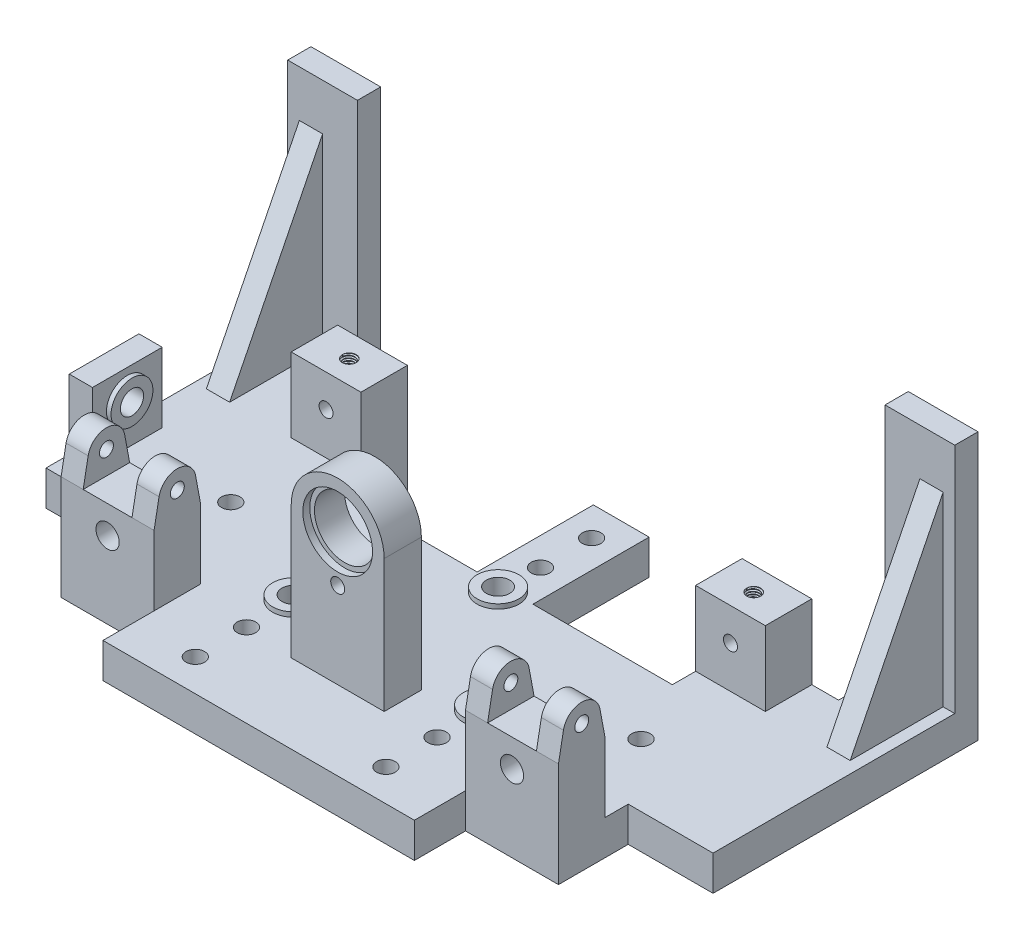
SolidWorks part; units mm, degrees
material "铸造碳钢"
ref_plane "前视基准面" through (0, 0, 0) normal (0, 0, 1) x (1, 0, 0)
ref_plane "上视基准面" through (0, 0, 0) normal (0, 1, 0) x (1, 0, 0)
ref_plane "右视基准面" through (0, 0, 0) normal (1, 0, 0) x (0, 0, -1)
sketch "草图1" plane through (0, 0, 0) normal (0, 1, 0) x (1, 0, 0)
  line L1 (-67, 0) -> (67, 0)
  line L9 (-143.5, 52) -> (-107, 52)
  line L10 (-107, 52) -> (-107, 22)
  line L11 (143.5, 52) -> (107, 52)
  line L12 (107, 52) -> (107, 22)
  line L13 (-107, 22) -> (-67, 22)
  line L14 (-67, 22) -> (-67, 0)
  line L15 (107, 22) -> (67, 22)
  line L16 (67, 22) -> (67, 0)
  line L21 (-72, 136) -> (-72, 106)
  line L22 (-72, 106) -> (-12, 106)
  line L25 (12, 106) -> (72, 106)
  line L26 (72, 106) -> (72, 136)
  line L27 (-12, 156) -> (-12, 106)
  line L28 (-12, 156) -> (12, 156)
  line L29 (12, 156) -> (12, 106)
  line L30 (-72, 136) -> (-143.5, 136)
  line L31 (-143.5, 136) -> (-143.5, 52)
  line L32 (72, 136) -> (143.5, 136)
  line L33 (143.5, 136) -> (143.5, 52)
  point P18 (0, 0)
  dimension "D2" = 60
  dimension "D3" = 71.5
  dimension "D4" = 84
  dimension "D5" = 60
  dimension "D6" = 50
  dimension "D7" = 287
  dimension "D8" = 71.5
  dimension "D9" = 36.5
  dimension "D10" = 76.5
  dimension "D11" = 36.5
  dimension "D12" = 76.5
  dimension "D13" = 22
  dimension "D14" = 52
  dimension "D18" = 30
extrude "凸台-拉伸1" add sketch "草图1" along normal blind 15
sketch "草图3" plane through (0, 15, 0) normal (0, 1, 0) x (1, 0, 0)
  line L0 (-133.5, 92) -> (-133.5, 62)
  line L1 (-133.5, 62) -> (-143.5, 62)
  line L2 (-143.5, 62) -> (-143.5, 92)
  line L3 (-143.5, 92) -> (-133.5, 92)
  line L4 (-67, 0) -> (67, 0) construction
  line L7 (-143.5, 136) -> (-143.5, 52) construction
  dimension "D1" = 30
  dimension "D2" = 10
  dimension "D3" = 62
extrude "凸台-拉伸2" add sketch "草图3" along normal blind 30
sketch "草图5" plane through (0, 15, 0) normal (0, 1, 0) x (1, 0, 0)
  line L0 (-107, 42) -> (-107, 22)
  line L1 (-107, 22) -> (-67, 22)
  line L2 (-67, 22) -> (-67, 42)
  line L3 (-67, 42) -> (-107, 42)
  line L4 (67, 42) -> (67, 22)
  line L5 (67, 22) -> (107, 22)
  line L6 (107, 22) -> (107, 42)
  line L7 (107, 42) -> (67, 42)
  line L8 (-67, 0) -> (67, 0) construction
  line L9 (-133.5, 62) -> (-133.5, 92) construction
  dimension "D1" = 20
  dimension "D2" = 40
  dimension "D3" = 20
  dimension "D4" = 40
  dimension "D5" = 42
  dimension "D6" = 42
  dimension "D7" = 26.5
  dimension "D8" = 134
extrude "凸台-拉伸3" add sketch "草图5" along normal blind 30
sketch "草图2" plane through (0, 15, 0) normal (0, 1, 0) x (1, 0, 0)
  line L0 (132.9483, 103) -> (219.6658, 103) construction
  line L1 (123.0215, 56) -> (237.8074, 56) construction
  line L2 (-41, 68.6858) -> (-41, 50.7818) construction
  line L3 (41, 68.6858) -> (41, 53.2784) construction
  line L4 (0, 122.8842) -> (0, 97.7435) construction
  line L6 (-133.5, 62) -> (-133.5, 92) construction
  line L7 (-67, 42) -> (-107, 42) construction
  circle A1 centre (0, 103) radius 5
  circle A2 centre (-41, 56) radius 5
  circle A3 centre (41, 56) radius 5
  dimension "D1" = 10
  dimension "D2" = 10
  dimension "D3" = 10
  dimension "D4" = 14
  dimension "D5" = 47
  dimension "D6" = 92.5
  dimension "D7" = 82
  dimension "D8" = 133.5
extrude "切除-拉伸1" cut sketch "草图2" against normal blind 13
sketch "草图4" plane through (-133.5, 0, 0) normal (1, 0, 0) x (0, 0, -1)
  line L0 (92, 45) -> (92, 15) construction
  line L1 (62, 15) -> (92, 15) construction
  circle A0 centre (77, 33) radius 5
  dimension "D1" = 10
  dimension "D2" = 15
  dimension "D3" = 18
extrude "切除-拉伸2" cut sketch "草图4" against normal up to next
sketch "草图6" plane through (0, 0, -42) normal (0, 0, -1) x (-1, 0, 0)
  line L0 (67, 15) -> (107, 15) construction
  line L1 (-107, 15) -> (-67, 15) construction
  line L2 (67, 45) -> (67, 15) construction
  line L3 (-67, 45) -> (-67, 15) construction
  circle A0 centre (87, 33) radius 5
  circle A1 centre (-87, 33) radius 5
  dimension "D1" = 10
  dimension "D2" = 10
  dimension "D3" = 18
  dimension "D4" = 18
  dimension "D5" = 20
  dimension "D6" = 20
extrude "切除-拉伸3" cut sketch "草图6" against normal up to next
sketch "草图7" plane through (-133.5, 0, 0) normal (1, 0, 0) x (0, 0, -1)
  circle A0 centre (77, 33) radius 9
  circle A1 centre (77, 33) radius 5 construction
  circle A2 centre (77, 33) radius 5
  dimension "D1" = 18
extrude "凸台-拉伸4" add sketch "草图7" along normal blind 2
sketch "草图8" plane through (0, 0, -42) normal (0, 0, -1) x (-1, 0, 0)
  circle A0 centre (87, 33) radius 5 construction
  circle A1 centre (-87, 33) radius 5 construction
  circle A2 centre (87, 33) radius 5
  circle A3 centre (-87, 33) radius 5
  circle A4 centre (-87, 33) radius 9
  circle A5 centre (87, 33) radius 9
  dimension "D1" = 18
  dimension "D2" = 18
extrude "凸台-拉伸5" add sketch "草图8" along normal blind 2
sketch "草图9" plane through (0, 15, 0) normal (0, 1, 0) x (1, 0, 0)
  circle A0 centre (-41, 56) radius 9
  circle A1 centre (0, 103) radius 9
  circle A2 centre (41, 56) radius 9
  circle A3 centre (-41, 56) radius 5 construction
  circle A4 centre (0, 103) radius 5 construction
  circle A5 centre (41, 56) radius 5 construction
  circle A6 centre (-41, 56) radius 5
  circle A7 centre (0, 103) radius 5
  circle A8 centre (41, 56) radius 5
  dimension "D1" = 18
  dimension "D2" = 18
  dimension "D3" = 18
extrude "凸台-拉伸6" add sketch "草图9" along normal blind 2
sketch "草图11" plane through (0, 15, 0) normal (0, 1, 0) x (1, 0, 0)
  line L0 (-133.5, 62) -> (-133.5, 92) construction
  line L1 (-20, 50) -> (20, 50)
  line L2 (-20, 50) -> (-20, 34)
  line L3 (-20, 34) -> (20, 34)
  line L4 (20, 50) -> (20, 34)
  line L7 (-67, 0) -> (67, 0) construction
  dimension "D1" = 40
  dimension "D2" = 16
  dimension "D3" = 113.5
  dimension "D4" = 34
extrude "凸台-拉伸7" add sketch "草图11" along normal blind 57
sketch "草图12" plane through (0, 72, 0) normal (0, 1, 0) x (1, 0, 0)
  line L5 (0, 34) -> (-20, 34)
  line L6 (-20, 34) -> (20, 34) construction
  line L7 (-20, 34) -> (-20, 50)
  line L8 (-20, 50) -> (0, 50)
  line L9 (20, 50) -> (-20, 50) construction
  line L10 (0, 50) -> (0, 34)
revolve "旋转1" add sketch "草图12" angle 180 about L10 reverse direction yes
sketch "草图13" plane through (0, 0, -34) normal (0, 0, 1) x (1, 0, 0)
  circle A0 centre (0, 72) radius 15
  arc A1 (20, 72) -> (-20, 72) centre (0, 72) ccw construction
  dimension "D1" = 30
extrude "切除-拉伸5" cut sketch "草图13" against normal blind 3 and the other way through all
sketch "草图14" plane through (0, 0, -37) normal (0, 0, 1) x (1, 0, 0)
  circle A0 centre (0, 72) radius 13
  dimension "D1" = 26
extrude "切除-拉伸6" cut sketch "草图14" against normal up to next
sketch "草图15" plane through (0, 0, -34) normal (0, 0, 1) x (1, 0, 0)
  circle A0 centre (0, 72) radius 20 construction
  circle A1 centre (0, 52) radius 3
  dimension "D1" = 40
  dimension "D2" = 6
extrude "切除-拉伸7" cut sketch "草图15" against normal blind 12
sketch "草图10" plane through (0, 15, 0) normal (0, 1, 0) x (1, 0, 0)
  line L0 (-67, 42) -> (-107, 42) construction
  line L1 (67, 42) -> (67, 22) construction
  line L2 (107, 42) -> (67, 42) construction
  line L3 (-67, 22) -> (-67, 42) construction
  line L4 (0, 103) -> (0, 157.8551) construction
  line L5 (-133.5, 62) -> (-133.5, 92) construction
  line L6 (-67, 42) -> (-107, 42) construction
  line L7 (107, 42) -> (67, 42) construction
  circle A0 centre (-41, 35.75) radius 4
  circle A1 centre (41, 35.75) radius 4
  circle A2 centre (-41, 13.75) radius 4
  circle A3 centre (41, 13.75) radius 4
  circle A6 centre (-91, 79) radius 4
  circle A7 centre (0, 121.25) radius 4
  circle A8 centre (0, 143.25) radius 4
  circle A9 centre (85.5, 79) radius 4
  circle A10 centre (0, 103) radius 5 construction
  dimension "D2" = 8
  dimension "D3" = 8
  dimension "D7" = 8
  dimension "D8" = 8
  dimension "D10" = 22
  dimension "D11" = 18.25
  dimension "D12" = 42.5
  dimension "D13" = 37
  dimension "D14" = 8
  dimension "D15" = 8
  dimension "D18" = 8
  dimension "D19" = 8
  dimension "D1" = 6.25
  dimension "D4" = 6.25
  dimension "D5" = 26
  dimension "D6" = 26
  dimension "D9" = 22
  dimension "D16" = 37
  dimension "D17" = 176.5
extrude "切除-拉伸4" cut sketch "草图10" against normal through all
ref_plane "基准面1" through (0, 45, 0) normal (0, 1, 0) x (1, 0, 0)
sketch "草图16" plane through (107, 0, 0) normal (1, 0, 0) x (0, 0, -1)
  line L0 (22, 45) -> (24.1352, 56.4648)
  line L1 (42, 45) -> (39.8648, 56.4648)
  line L2 (22, 45) -> (42, 45) construction
  line L3 (22, 45) -> (42, 45)
  arc A2 (39.8648, 56.4648) -> (24.1352, 56.4648) centre (32, 55) ccw
  dimension "D1" = 10
  dimension "D2" = 16
  dimension "D3" = 10
extrude "凸台-拉伸8" add sketch "草图16" against normal blind 40
sketch "草图17" plane through (45, 45, 0) normal (0, -1, 0) x (0, 0, -1)
  line L1 (42, 62) -> (42, 22) construction
  line L2 (42, 52.5) -> (22, 52.5)
  line L6 (42, 52.5) -> (42, 31.5)
  line L7 (42, 31.5) -> (22, 31.5)
  line L17 (22, 52.5) -> (22, 31.5)
  line L18 (22, 22) -> (22, 62) construction
  line L19 (39.8648, 62) -> (24.1352, 62) construction
  line L20 (24.1352, 22) -> (39.8648, 22) construction
  dimension "D1" = 9.5
  dimension "D2" = 9.5
extrude "切除-拉伸8" cut sketch "草图17" against normal up to next
sketch "草图18" plane through (107, 0, 0) normal (1, 0, 0) x (0, 0, -1)
  circle A0 centre (32, 55) radius 3
  arc A2 (39.8648, 56.4648) -> (24.1352, 56.4648) centre (32, 55) ccw construction
  dimension "D1" = 6
extrude "切除-拉伸9" cut sketch "草图18" along direction (1, 0, 0) on the side against the normal up to surface (40 mm away) up to face at (67, 39.9108, -32)
mirror "镜向1" about plane through (0, 0, 0) normal (1, 0, 0) of "切除-拉伸9", "切除-拉伸8", "凸台-拉伸8"
sketch "草图19" plane through (0, 15, 0) normal (0, 1, 0) x (1, 0, 0)
  line L17 (-72, 136) -> (-102, 136)
  line L18 (-72, 136) -> (-72, 116)
  line L19 (-72, 116) -> (-102, 116)
  line L20 (-102, 136) -> (-102, 116)
  line L21 (72, 136) -> (102, 136)
  line L22 (72, 136) -> (72, 116)
  line L23 (72, 116) -> (102, 116)
  line L24 (102, 136) -> (102, 116)
  dimension "D1" = 20
  dimension "D2" = 30
  dimension "D3" = 30
  dimension "D4" = 20
extrude "凸台-拉伸9" add sketch "草图19" along normal blind 32
sketch "草图20" plane through (0, 0, -136) normal (0, 0, -1) x (-1, 0, 0)
  line L4 (-102, 47) -> (-102, 15) construction
  line L5 (-102, 47) -> (-72, 47) construction
  line L7 (72, 47) -> (72, 0) construction
  line L8 (72, 47) -> (102, 47) construction
  circle A0 centre (-87, 33) radius 3
  circle A1 centre (87, 33) radius 3
  dimension "D1" = 6
  dimension "D2" = 6
  dimension "D3" = 15
  dimension "D4" = 14
  dimension "D5" = 14
  dimension "D6" = 15
extrude "切除-拉伸10" cut sketch "草图20" against normal blind 20
sketch "草图21" plane through (0, 0, -136) normal (0, 0, -1) x (-1, 0, 0)
  line L0 (-143.5, 15) -> (-143.5, 0)
  line L1 (-143.5, 0) -> (-113.5, 0)
  line L2 (-143.5, 0) -> (-72, 0) construction
  line L3 (-113.5, 0) -> (-113.5, 15)
  line L4 (-143.5, 15) -> (-102, 15) construction
  line L5 (-113.5, 15) -> (-143.5, 15)
  line L6 (143.5, 15) -> (113.5, 15)
  line L7 (102, 15) -> (143.5, 15) construction
  line L8 (113.5, 15) -> (113.5, 0)
  line L9 (72, 0) -> (143.5, 0) construction
  line L10 (113.5, 0) -> (143.5, 0)
  line L11 (143.5, 0) -> (143.5, 15)
  dimension "D1" = 30
  dimension "D2" = 30
extrude "凸台-拉伸10" add sketch "草图21" along normal blind 30
sketch "草图22" plane through (0, 15, 0) normal (0, 1, 0) x (1, 0, 0)
  line L0 (-143.5, 166) -> (-143.5, 156)
  line L1 (-143.5, 166) -> (-143.5, 92) construction
  line L2 (-143.5, 156) -> (-113.5, 156)
  line L3 (-113.5, 166) -> (-113.5, 136) construction
  line L4 (-113.5, 156) -> (-113.5, 166)
  line L5 (-113.5, 166) -> (-143.5, 166)
  line L6 (113.5, 166) -> (113.5, 156)
  line L7 (113.5, 166) -> (113.5, 136) construction
  line L8 (113.5, 156) -> (143.5, 156)
  line L9 (143.5, 52) -> (143.5, 166) construction
  line L10 (143.5, 156) -> (143.5, 166)
  line L11 (143.5, 166) -> (113.5, 166)
  dimension "D1" = 10
extrude "凸台-拉伸11" add sketch "草图22" along normal blind 100
sketch "草图24" plane through (0, 47, 0) normal (0, 1, 0) x (1, 0, 0)
  line L0 (102, 136) -> (72, 136) construction
  line L1 (72, 136) -> (72, 116) construction
  line L2 (-102, 136) -> (-102, 116) construction
  line L3 (-72, 136) -> (-102, 136) construction
  circle A0 centre (-87, 126) radius 3
  circle A1 centre (87, 126) radius 3
  dimension "D1" = 6
  dimension "D4" = 6
  dimension "D2" = 10
  dimension "D3" = 15
  dimension "D5" = 15
  dimension "D6" = 10
extrude "切除-拉伸12" cut sketch "草图24" against normal blind 10
ref_plane "基准面2" through (133.5, 0, 0) normal (1, 0, 0) x (0, 0, -1)
sketch "草图25" plane through (133.5, 0, 0) normal (1, 0, 0) x (0, 0, -1)
  line L0 (156, 95) -> (116, 15)
  line L1 (156, 115) -> (156, 15) construction
  line L2 (52, 15) -> (156, 15) construction
  dimension "D1" = 40
  dimension "D2" = 80
rib "筋1" sketch "草图25" sketch "草图25" thickness 10 extrusion direction parallel to sketch draft on no parameters "D1"=10
mirror "镜向2" about plane through (0, 0, 0) normal (1, 0, 0) of "筋1"
thread "螺纹线1" pitch 1 method extrude profile "螺纹线轮廓1" start angle 0, offset 0, length 8, pitch 1, diameter 6
ref_plane "基准面3" through (-90, 47, -126) normal (0, 0, 1) x (-1, 0, 0)
sketch "螺纹线轮廓1" plane through (-90, 47, -126) normal (0, 0, 1) x (-1, 0, 0)
  line L0 (0, 0) -> (0, 1) construction
  line L11 (0, 0) -> (0, 0.875)
  line L12 (0, 0.875) -> (-0.5413, 0.5625)
  line L13 (-0.5413, 0.5625) -> (-0.5413, 0.3125)
  line L15 (-0.5413, 0.3125) -> (0, 0)
  line L17 (-0.5413, 0.4375) -> (0, 0.4375) construction
  point P2 (0, 0)
  dimension "Pitch" = 1
  dimension "Profile_Angle" = 60
  dimension "Profile_Land" = 0.25
  dimension "Profile_Height" = 0.5413
thread "螺纹线2" pitch 1 method extrude profile "螺纹线轮廓2" start angle 0, offset 0, length 8, pitch 1, diameter 6
ref_plane "基准面4" through (84, 47, -126) normal (0, 0, 1) x (-1, 0, 0)
sketch "螺纹线轮廓2" plane through (84, 47, -126) normal (0, 0, 1) x (-1, 0, 0)
  line L0 (0, 0) -> (0, 1) construction
  line L11 (0, 0) -> (0, 0.875)
  line L12 (0, 0.875) -> (-0.5413, 0.5625)
  line L13 (-0.5413, 0.5625) -> (-0.5413, 0.3125)
  line L15 (-0.5413, 0.3125) -> (0, 0)
  line L17 (-0.5413, 0.4375) -> (0, 0.4375) construction
  point P2 (0, 0)
  dimension "Pitch" = 1
  dimension "Profile_Angle" = 60
  dimension "Profile_Land" = 0.25
  dimension "Profile_Height" = 0.5413
